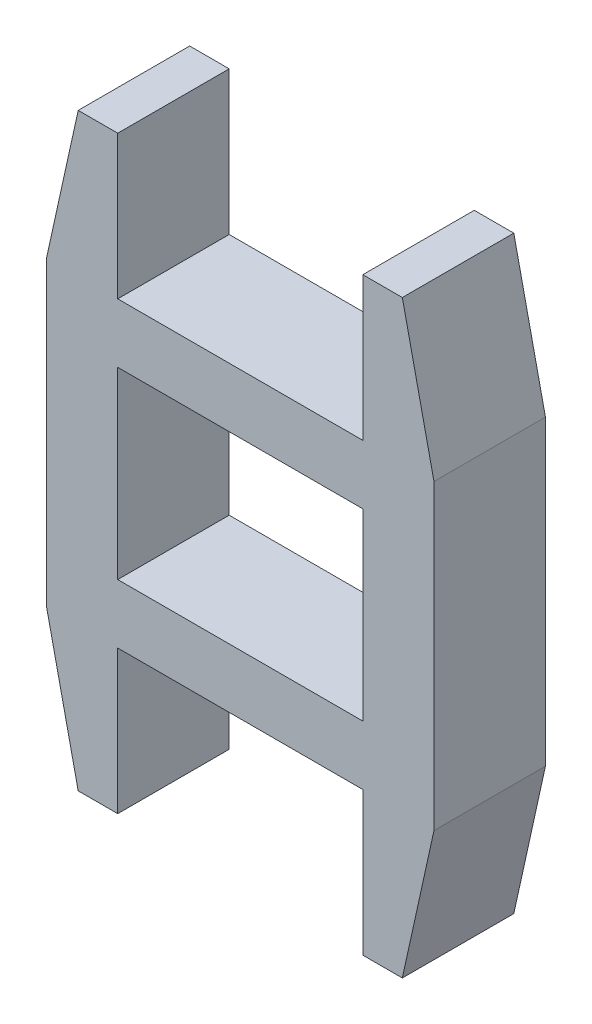
SolidWorks part; units mm, degrees
material "Acrylic (Medium-high impact)"
ref_plane "Front Plane" through (0, 0, 0) normal (0, 0, 1) x (1, 0, 0)
ref_plane "Top Plane" through (0, 0, 0) normal (0, 1, 0) x (1, 0, 0)
ref_plane "Right Plane" through (0, 0, 0) normal (1, 0, 0) x (0, 0, -1)
sketch "Sketch1" plane through (0, 0, 0) normal (0, 0, 1) x (1, 0, 0)
  line L0 (1247.2096, 960.5272) -> (1247.2096, 951.2272)
  line L1 (1263.2096, 949.7272) -> (1243.6096, 949.7272) construction
  line L2 (1247.2096, 948.2272) -> (1243.6096, 948.2272) construction
  line L3 (1247.2096, 960.5272) -> (1259.6096, 960.5272)
  line L4 (1245.2096, 970.7864) -> (1247.2096, 970.7864)
  line L5 (1247.2096, 970.7864) -> (1247.2096, 963.5272)
  line L6 (1247.2096, 955.8772) -> (1259.6096, 955.8772) construction
  line L7 (1259.6096, 963.5272) -> (1247.2096, 963.5272)
  line L8 (1243.6096, 963.5272) -> (1243.6096, 948.2272)
  line L9 (1243.6096, 948.2272) -> (1245.2096, 940.968)
  line L10 (1247.2096, 963.5272) -> (1243.6096, 963.5272) construction
  line L11 (1259.6096, 948.2272) -> (1247.2096, 948.2272)
  line L12 (1243.6096, 963.5272) -> (1245.2096, 970.7864)
  line L13 (1247.2096, 940.968) -> (1247.2096, 948.2272)
  line L14 (1245.2096, 940.968) -> (1247.2096, 940.968)
  line L15 (1247.2096, 951.2272) -> (1259.6096, 951.2272)
  line L16 (1259.6096, 963.5272) -> (1263.2096, 963.5272) construction
  line L17 (1259.6096, 948.2272) -> (1263.2096, 948.2272) construction
  line L18 (1261.6096, 940.968) -> (1259.6096, 940.968)
  line L19 (1253.4096, -37.9351) -> (1253.4096, 49962.0649) construction
  line L20 (1259.6096, 940.968) -> (1259.6096, 948.2272)
  line L21 (1263.2096, 963.5272) -> (1261.6096, 970.7864)
  line L22 (1263.2096, 948.2272) -> (1261.6096, 940.968)
  line L23 (1263.2096, 963.5272) -> (1263.2096, 948.2272)
  line L24 (1259.6096, 970.7864) -> (1259.6096, 963.5272)
  line L25 (1261.6096, 970.7864) -> (1259.6096, 970.7864)
  line L26 (1263.2096, 962.0272) -> (1243.6096, 962.0272) construction
  line L27 (1259.6096, 960.5272) -> (1259.6096, 951.2272)
  point P2 (1263.2096, 955.8772)
  point P14 (1243.6096, 955.8772)
  point P15 (1253.4096, 963.5272)
  point P20 (1253.4096, 962.0272)
  point P26 (1253.4096, 955.8772)
  point P28 (1253.4096, 963.5272)
  point P30 (1253.4096, 960.5272)
  point P31 (1253.4096, 949.7272)
  point P33 (1253.4096, 951.2272)
  point P36 (1253.4096, 948.2272)
  point P38 (1253.4096, 960.5272)
  dimension "D1" = 6.2
  dimension "D2" = 7.2592
  dimension "D3" = 2
  dimension "D4" = 3
  dimension "D5" = 7.65
  dimension "D8" = 3.6
extrude "Boss-Extrude1" add sketch "Sketch1" along normal blind 5.64
